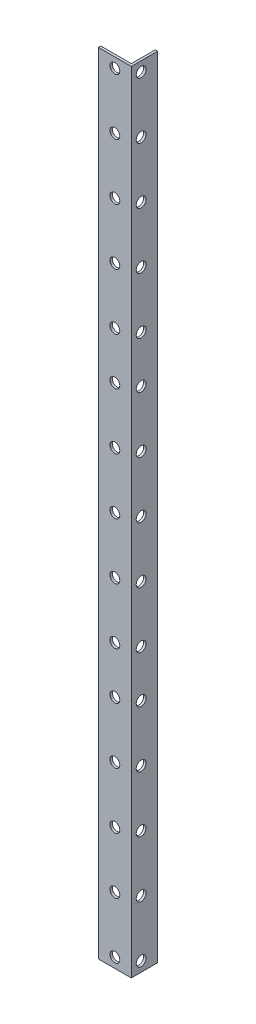
SolidWorks part; units mm, degrees
material "6061-T6 (SS)"
ref_plane "Alzado" through (0, 0, 0) normal (0, 0, 1) x (1, 0, 0)
ref_plane "Planta" through (0, 0, 0) normal (0, 1, 0) x (1, 0, 0)
ref_plane "Vista lateral" through (0, 0, 0) normal (1, 0, 0) x (0, 0, -1)
sketch "Sketch1" plane through (0, 0, 0) normal (0, 1, 0) x (1, 0, 0)
  line L0 (0, 0) -> (15, 0)
  line L1 (15, 0) -> (15, 12)
  line L2 (15, 12) -> (13.9, 12)
  line L3 (13.9, 12) -> (13.9, 1.1)
  line L4 (13.9, 1.1) -> (0, 1.1)
  line L5 (0, 1.1) -> (0, 0)
  dimension "D1" = 15
  dimension "D2" = 12
  dimension "D3" = 1.1
  dimension "D4" = 1.1
extrude "Boss-Extrude1" add sketch "Sketch1" along normal blind 360
sketch "Sketch2" plane through (13.9, 0, 0) normal (-1, 0, 0) x (0, 0, 1)
  circle A1 centre (-4.5, 329.8125) radius 2.25
  circle A2 centre (-4.5, 304.125) radius 2.25
  circle A3 centre (-4.5, 278.4375) radius 2.25
  circle A4 centre (-4.5, 252.75) radius 2.25
  circle A5 centre (-4.5, 231.375) radius 2.25
  circle A6 centre (-4.5, 205.6875) radius 2.25
  circle A7 centre (-4.5, 180) radius 2.25
  circle A8 centre (-4.5, 154.3125) radius 2.25
  circle A9 centre (-4.5, 128.625) radius 2.25
  circle A10 centre (-4.5, 107.25) radius 2.25
  circle A11 centre (-4.5, 81.5625) radius 2.25
  circle A12 centre (-4.5, 55.875) radius 2.25
  circle A13 centre (-4.5, 30.1875) radius 2.25
  circle A14 centre (-4.5, 4.5) radius 2.25
  circle A15 centre (-4.5, 355.5) radius 2.25
  point P0 (0, 0)
  dimension "D1" = 4.5
extrude "Cut-Extrude1" cut sketch "Sketch2" against normal up to next
sketch "Sketch3" plane through (0, 0, 0) normal (0, 0, 1) x (1, 0, 0)
  line L0 (-218, 242.75) -> (18, 242.75) construction
  line L2 (18, 363) -> (18, -3) construction
  line L3 (-65, 263) -> (-10, 263) construction
  line L4 (-10, 222.5) -> (-65, 222.5) construction
  line L5 (-218, 117.25) -> (18, 117.25) construction
  line L6 (-218, -3) -> (-218, 363) construction
  line L7 (-65, 137.5) -> (-10, 137.5) construction
  line L8 (-10, 97) -> (-65, 97) construction
  circle A15 centre (7.5, 355.5) radius 2.25
  point P14 (0, 0)
  point P15 (0, 0)
  point P16 (5.5, 355.5)
  point P17 (0, 0)
  point P18 (0, 0)
  point P19 (7.5, 355.5)
  point P20 (0, 0)
  point P21 (-213.9, 242.75)
  point P22 (-218, 242.75)
  dimension "D1" = 4.5
extrude "Cut-Extrude2" cut sketch "Sketch3" against normal up to next
sketch "Sketch4" plane through (0, 0, 0) normal (0, 0, 1) x (1, 0, 0)
  line L0 (18, 242.75) -> (-100, 242.75) construction
  line L1 (-218, 242.75) -> (18, 242.75) construction
  line L2 (18, 117.25) -> (-100, 117.25) construction
  line L3 (-218, 117.25) -> (18, 117.25) construction
pattern_linear "LPattern1" count 5 spacing 25.6562 along (0, -1, 0) of "Cut-Extrude2"
pattern_linear "LPattern2" count 3 spacing 124.1875 along (0, -1, 0) of "LPattern1"
